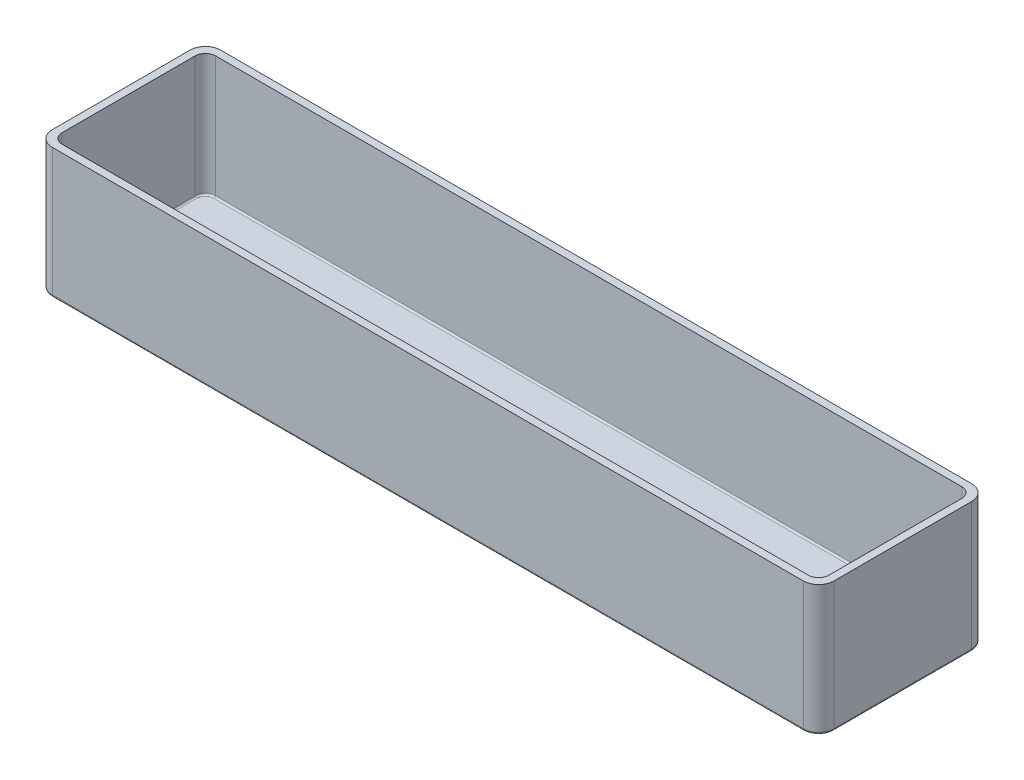
SolidWorks part; units mm, degrees
material "NEOPRENE"
ref_plane "Front" through (0, 0, 0) normal (0, 0, 1) x (1, 0, 0)
ref_plane "Top" through (0, 0, 0) normal (0, 1, 0) x (1, 0, 0)
ref_plane "Right" through (0, 0, 0) normal (1, 0, 0) x (0, 0, -1)
sketch "Sketch1" plane through (0, 0, 0) normal (0, 1, 0) x (1, 0, 0)
  line L0 (-119.0625, 0) -> (-121.3993, 0) construction
  line L1 (-121.3993, 26.1493) -> (121.3993, 26.1493)
  line L2 (-121.3993, 26.1493) -> (-121.3993, -26.1493)
  line L3 (-121.3993, -26.1493) -> (121.3993, -26.1493)
  line L4 (121.3993, 26.1493) -> (121.3993, -26.1493)
  line L5 (-121.3993, 26.1493) -> (121.3993, -26.1493) construction
  line L6 (-121.3993, -26.1493) -> (121.3993, 26.1493) construction
  line L7 (119.0625, 23.8125) -> (-119.0625, 23.8125)
  line L8 (119.0625, 23.8125) -> (119.0625, -23.8125)
  line L9 (119.0625, -23.8125) -> (-119.0625, -23.8125)
  line L10 (-119.0625, 23.8125) -> (-119.0625, -23.8125)
  line L11 (119.0625, 23.8125) -> (-119.0625, -23.8125) construction
  line L12 (119.0625, -23.8125) -> (-119.0625, 23.8125) construction
  line L13 (0, 23.8125) -> (0, 26.1493) construction
  point P0 (0, 0)
  point P6 (0, 0)
  dimension "D1" = 238.125
  dimension "D2" = 47.625
  dimension "THICKNESS" = 2.3368
extrude "Boss-Extrude1" add sketch "Sketch1" along normal blind 38.1
sketch "Sketch2" plane through (0, 0, 0) normal (0, -1, 0) x (1, 0, 0)
  line L4 (121.3993, -26.1493) -> (121.3993, 26.1493)
  line L5 (121.3993, 26.1493) -> (-121.3993, 26.1493)
  line L6 (-121.3993, 26.1493) -> (-121.3993, -26.1493)
  line L7 (-121.3993, -26.1493) -> (121.3993, -26.1493)
  line L8 (121.3993, -26.1493) -> (121.3993, 26.1493)
  line L9 (121.3993, 26.1493) -> (-121.3993, 26.1493)
  line L10 (-121.3993, 26.1493) -> (-121.3993, -26.1493)
  line L11 (-121.3993, -26.1493) -> (121.3993, -26.1493)
  arc A0 (105.1493, 1.8243) -> (105.1493, 6.0243) centre (105.1493, 3.9243) ccw construction
  arc A1 (105.1493, 6.0243) -> (105.1493, 1.8243) centre (105.1493, 3.9243) ccw construction
  arc A2 (74.1493, 1.8243) -> (74.1493, 6.0243) centre (74.1493, 3.9243) ccw construction
  arc A3 (74.1493, 6.0243) -> (74.1493, 1.8243) centre (74.1493, 3.9243) ccw construction
  arc A4 (105.1493, 1.8243) -> (105.1493, 6.0243) centre (105.1493, 3.9243) ccw
  arc A5 (105.1493, 6.0243) -> (105.1493, 1.8243) centre (105.1493, 3.9243) ccw
  arc A6 (74.1493, 1.8243) -> (74.1493, 6.0243) centre (74.1493, 3.9243) ccw
  arc A7 (74.1493, 6.0243) -> (74.1493, 1.8243) centre (74.1493, 3.9243) ccw
  dimension "D1" = 0
extrude "Boss-Extrude2" add sketch "Sketch2" along normal blind 2.3368
fillet "Fillet1" radius 3.175 4 edges at (119.0625, 19.05, -23.8125) (119.0625, 19.05, 23.8125) (-119.0625, 19.05, 23.8125) (-119.0625, 19.05, -23.8125)
fillet "Fillet2" radius 4.7625 4 edges at (-121.3993, 17.8816, -26.1493) (121.3993, 17.8816, -26.1493) (121.3993, 17.8816, 26.1493) (-121.3993, 17.8816, 26.1493)
sketch "Sketch4" plane through (0, -2.3368, 0) normal (0, -1, 0) x (1, 0, 0)
  line L2 (121.3993, -21.3868) -> (121.3993, 21.3868) construction
  line L3 (116.6368, 26.1493) -> (-116.6368, 26.1493) construction
  circle A0 centre (89.6493, 3.9243) radius 12.065
  dimension "D1" = 24.13
  dimension "D3" = 22.225
  dimension "D2" = 31.75
extrude "Cut-Extrude2" cut sketch "Sketch4" against normal through all
sketch "Sketch5" plane through (0, 0, -23.8125) normal (0, 0, 1) x (1, 0, 0)
  line L0 (0, 0) -> (0, 19.05) construction
  line L1 (115.8875, 38.1) -> (-115.8875, 38.1) construction
  line L2 (-92.075, 0) -> (92.075, 0)
  line L3 (-92.075, 0) -> (-92.075, 38.1)
  line L4 (-92.075, 38.1) -> (92.075, 38.1)
  line L5 (92.075, 0) -> (92.075, 38.1)
  line L6 (-92.075, 0) -> (92.075, 38.1) construction
  line L7 (-92.075, 38.1) -> (92.075, 0) construction
  line L8 (115.8875, 0) -> (-115.8875, 0) construction
  dimension "D1" = 184.15
extrude "Boss-Extrude3" [suppressed] add sketch "Sketch5" along normal blind 1.651
fillet "Fillet3" [suppressed] radius 0.381
fillet "Fillet4" radius 0.508 8 edges at (118.1326, 0, -22.8826) (119.0625, 0, 0) (118.1326, 0, 22.8826) (0, 0, 23.8125) (-118.1326, 0, 22.8826) (-119.0625, 0, 0) (-118.1326, 0, -22.8826) (0, 0, -23.8125)
fillet "Fillet5" radius 0.762 8 edges at (-120.0044, -2.3368, 24.7544) (0, -2.3368, 26.1493) (120.0044, -2.3368, 24.7544) (121.3993, -2.3368, 0) (120.0044, -2.3368, -24.7544) (0, -2.3368, -26.1493) (-120.0044, -2.3368, -24.7544) (-121.3993, -2.3368, 0)
sketch "Sketch6" [suppressed] plane through (0, -2.3368, 0) normal (0, -1, 0) x (1, 0, 0)
  circle A0 centre (73.8445, 3.6195) radius 2.1 construction
  circle A1 centre (73.8445, 3.6195) radius 2.1
  circle A2 centre (104.8445, 3.6195) radius 2.1 construction
  circle A3 centre (104.8445, 3.6195) radius 2.1
extrude "Boss-Extrude4" [suppressed] add sketch "Sketch6" against normal up to surface (2.3368 mm away) up to face at (0, 0, 0)
sketch "Sketch7" [suppressed] plane through (0, -2.3368, 0) normal (0, -1, 0) x (1, 0, 0)
  circle A0 centre (-45.2, 0.936) radius 12.192
  circle A1 centre (45, 0.936) radius 12.192
  dimension "D1" = 24.384
extrude "Cut-Extrude3" [suppressed] cut sketch "Sketch7" against normal through all
sketch "Sketch8" [suppressed] plane through (0, 38.1, 0) normal (0, 1, 0) x (1, 0, 0)
  line L25 (-156.7727, 50.8) -> (156.7727, 50.8)
  line L26 (-156.7727, 50.8) -> (-156.7727, -50.8)
  line L27 (-156.7727, -50.8) -> (156.7727, -50.8)
  line L28 (156.7727, 50.8) -> (156.7727, -50.8)
  line L29 (-156.7727, 50.8) -> (156.7727, -50.8) construction
  line L30 (-156.7727, -50.8) -> (156.7727, 50.8) construction
  point P15 (0, 0)
  dimension "D2" = 101.6
  dimension "D1" = 313.5454
extrude "Cut-Extrude4" [suppressed] cut sketch "Sketch8" against normal blind 9.525
sketch "Sketch9" [suppressed] plane through (0, 0, 0) normal (0, 1, 0) x (1, 0, 0)
  line L1 (141.011, 38.276) -> (-141.011, 38.276)
  line L2 (141.011, 38.276) -> (141.011, -38.276)
  line L3 (141.011, -38.276) -> (-141.011, -38.276)
  line L4 (-141.011, 38.276) -> (-141.011, -38.276)
  line L5 (141.011, 38.276) -> (-141.011, -38.276) construction
  line L6 (141.011, -38.276) -> (-141.011, 38.276) construction
  point P0 (0, 0)
  dimension "D1" = 76.552
  dimension "D2" = 282.022
extrude "Cut-Extrude5" [suppressed] cut sketch "Sketch9" along normal offset from surface 2.54 and the other way through all up to face at (0, 38.1, 0)
sketch "Sketch10" [suppressed] plane through (0, 0, 0) normal (0, 1, 0) x (1, 0, 0)
  line L1 (-134.0132, -36.4455) -> (134.0132, -36.4455)
  line L2 (-134.0132, -36.4455) -> (-134.0132, 36.4455)
  line L3 (-134.0132, 36.4455) -> (134.0132, 36.4455)
  line L4 (134.0132, -36.4455) -> (134.0132, 36.4455)
  line L5 (-134.0132, -36.4455) -> (134.0132, 36.4455) construction
  line L6 (-134.0132, 36.4455) -> (134.0132, -36.4455) construction
  point P0 (0, 0)
  dimension "D1" = 268.0264
  dimension "D2" = 72.8909
extrude "Cut-Extrude6" [suppressed] cut sketch "Sketch10" along normal through all
sketch "Sketch11" [suppressed] plane through (0, -2.3368, 0) normal (0, -1, 0) x (1, 0, 0)
  line L1 (-127.2014, -33.7924) -> (127.2014, -33.7924)
  line L2 (-127.2014, -33.7924) -> (-127.2014, 33.7924)
  line L3 (-127.2014, 33.7924) -> (127.2014, 33.7924)
  line L4 (127.2014, -33.7924) -> (127.2014, 33.7924)
  line L5 (-127.2014, -33.7924) -> (127.2014, 33.7924) construction
  line L6 (-127.2014, 33.7924) -> (127.2014, -33.7924) construction
  point P0 (0, 0)
  dimension "D1" = 254.4028
  dimension "D2" = 67.5847
extrude "Cut-Extrude7" [suppressed] cut sketch "Sketch11" against normal offset from surface (37.8968 mm away) 2.54 up to face at (0, 38.1, 0)
sketch "Sketch12" [suppressed] plane through (0, 0, 0) normal (0, 1, 0) x (1, 0, 0)
  line L1 (-131.4623, -33.804) -> (131.4623, -33.804)
  line L2 (-131.4623, -33.804) -> (-131.4623, 33.804)
  line L3 (-131.4623, 33.804) -> (131.4623, 33.804)
  line L4 (131.4623, -33.804) -> (131.4623, 33.804)
  line L5 (-131.4623, -33.804) -> (131.4623, 33.804) construction
  line L6 (-131.4623, 33.804) -> (131.4623, -33.804) construction
  point P0 (0, 0)
  dimension "D1" = 262.9246
  dimension "D2" = 67.6081
extrude "Cut-Extrude8" [suppressed] cut sketch "Sketch12" along normal through all
sketch "Sketch13" [suppressed] plane through (0, 0, 23.8125) normal (0, 0, -1) x (-1, 0, 0)
  line L0 (64.6891, 28.575) -> (64.6891, -2.3368)
  line L1 (115.8875, 28.575) -> (-115.8875, 28.575) construction
  line L2 (-116.6368, -2.3368) -> (116.6368, -2.3368) construction
  dimension "D1" = 30.9118
equation "\"D1@Boss-Extrude2\"=\"THICKNESS\""
